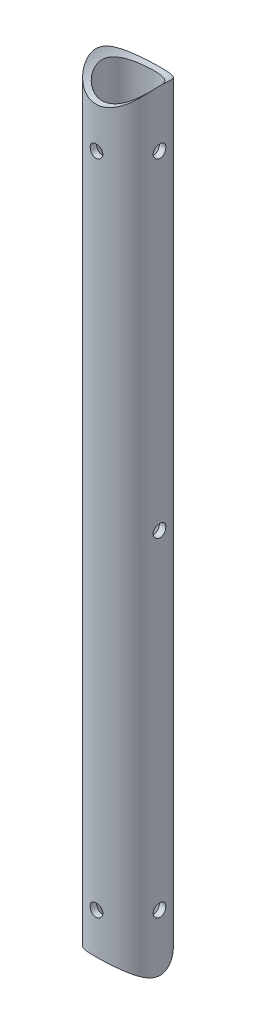
SolidWorks part; units mm, degrees
ref_plane "Front Plane" through (0, 0, 0) normal (0, 0, 1) x (1, 0, 0)
ref_plane "Top Plane" through (0, 0, 0) normal (0, 1, 0) x (1, 0, 0)
ref_plane "Right Plane" through (0, 0, 0) normal (1, 0, 0) x (0, 0, -1)
sketch "Sketch1" plane through (0, 0, 0) normal (0, 1, 0) x (1, 0, 0)
  circle A0 centre (0, 0) radius 12.7
  circle A1 centre (0, 0) radius 10.287
  dimension "D1" = 25.4
  dimension "D2" = 2.413
extrude "Boss-Extrude1" add sketch "Sketch1" along normal blind 152.4 and the other way blind 152.4
sketch "Sketch2" plane through (0, 0, 0) normal (0, 0, 1) x (1, 0, 0)
  line L0 (0, 161.925) -> (0, -161.925) construction
  line L1 (12.7, 152.4) -> (-12.7, 152.4) construction
  line L2 (-12.7, -152.4) -> (12.7, -152.4) construction
  line L3 (-12.7, -152.4) -> (-12.7, 152.4) construction
  line L4 (-12.7, 152.4) -> (12.7, 152.4) construction
  line L5 (12.7, -152.4) -> (12.7, 152.4) construction
  line L6 (-12.7, -152.4) -> (12.7, 152.4) construction
  line L7 (-12.7, 152.4) -> (12.7, -152.4) construction
  line L8 (12.7, 152.4) -> (-12.7, 152.4) construction
  circle A0 centre (0, 161.925) radius 15.875
  circle A1 centre (0, -161.925) radius 15.875
  circle A2 centre (0, 130) radius 2.5
  circle A3 centre (0, -130) radius 2.5
  point P6 (0, 0)
  dimension "D1" = 31.75
  dimension "D4" = 130
  dimension "D6" = 5
  dimension "D2" = 25.4
  dimension "D3" = 323.85
  dimension "D5" = 260
extrude "Cut-Extrude1" cut sketch "Sketch2" against normal blind 152.4 and the other way blind 152.4
sketch "Sketch3" plane through (0, 0, 0) normal (1, 0, 0) x (0, 0, -1)
  line L0 (0, 130) -> (0, -130) construction
  circle A0 centre (0, 130) radius 2.5
  circle A1 centre (0, -130) radius 2.5
  dimension "D2" = 5
  dimension "D1" = 260
extrude "Cut-Extrude2" cut sketch "Sketch3" against normal blind 50 and the other way blind 50
sketch "Sketch4" plane through (0, 0, 0) normal (1, 0, 0) x (0, 0, -1)
  circle A0 centre (0, 0) radius 2.5
  dimension "D1" = 5
extrude "Cut-Extrude3" cut sketch "Sketch4" against normal blind 30 and the other way blind 30
